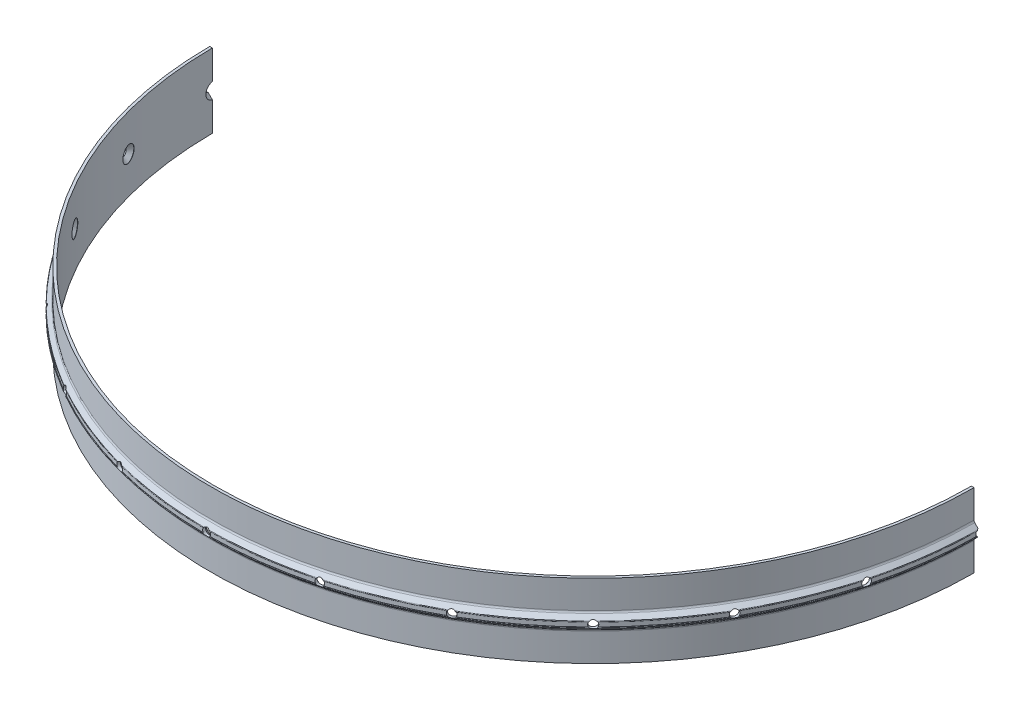
SolidWorks part; units mm, degrees
ref_plane "Front Plane" through (0, 0, 0) normal (0, 0, 1) x (1, 0, 0)
ref_plane "Top Plane" through (0, 0, 0) normal (0, 1, 0) x (1, 0, 0)
ref_plane "Right Plane" through (0, 0, 0) normal (1, 0, 0) x (0, 0, -1)
sketch "Sketch1" plane through (0, 0, 0) normal (0, 0, 1) x (1, 0, 0)
  line L0 (144.7, 34.35) -> (144.7, 23.2858)
  line L1 (-152.4, 34.35) -> (152.4, 34.35) construction
  line L2 (144.7, 23.2858) -> (146.6222, 21.3636)
  line L3 (146.6222, 21.3636) -> (146.4, 21.1414)
  line L4 (146.4, 21.1414) -> (146.4, 19.5586)
  line L5 (146.4, 19.5586) -> (146.6222, 19.3364)
  line L6 (146.6222, 19.3364) -> (144.7, 17.4142)
  line L7 (144.7, 17.4142) -> (144.7, 6.35)
  line L8 (152.4, 6.35) -> (-152.4, 6.35) construction
  line L9 (144.7, 34.35) -> (143.7, 34.35)
  line L10 (146.9107, 34.35) -> (-147.4, 34.35) construction
  line L11 (143.7, 34.35) -> (143.7, 6.35)
  line L12 (143.7, 6.35) -> (144.7, 6.35)
  line L13 (147.4, 22) -> (147.4, 34.35) construction
  line L16 (147.4, 18.7) -> (146.4, 19.7) construction
  line L17 (146.4, 21) -> (147.4, 22) construction
  line L19 (146.4, 19.7) -> (146.4, 21) construction
  line L20 (0, 0) -> (0, 37.398) construction
  line L21 (152.4, 37.398) -> (-152.4, 37.398) construction
  dimension "D1" = 1
  dimension "D2" = 2.7
  dimension "D3" = 0.1
  dimension "D4" = 0.1
  dimension "D5" = 1
  dimension "D6" = 0
revolve "Revolve1" add sketch "Sketch1" angle 180 about L20
sketch "Sketch2" plane through (0, 0, 0) normal (0, 0, 1) x (1, 0, 0)
  circle A0 centre (0, 20.35) radius 1.5
  dimension "D1" = 3
extrude "Cut-Extrude2" cut sketch "Sketch2" along normal through all
sketch "Sketch3" plane through (0, 0, 0) normal (0, 0, 1) x (1, 0, 0)
  circle A0 centre (0, 20.35) radius 3
  dimension "D1" = 6
extrude "Cut-Extrude3" cut sketch "Sketch3" along normal blind 143.764
chamfer "Chamfer1" distance 1.5 angle 45 1 edges at (1.5, 20.35, 143.764)
fillet "Fillet1" radius 0.25 4 edges at (104.0677, 21.3636, 103.2859) (104.0677, 19.3364, 103.2859) (-104.0677, 19.3364, 103.2859) (-104.0677, 21.3636, 103.2859)
fillet "Fillet2" radius 1 2 edges at (0, 17.4142, 144.7) (0, 23.2858, 144.7)
pattern_circular "CirPattern1" count 7 every 15 about axis through (0, 0, 0) along (0, 1, 0) of "Cut-Extrude3", "Cut-Extrude2", "Chamfer1"
sketch "Sketch4" plane through (0, 34.35, 0) normal (0, 1, 0) x (1, 0, 0)
  line L0 (144.7, 0) -> (143.7, 0) construction
  line L1 (164.2641, -0.5) -> (-176.002, -0.5)
  line L2 (164.2641, -0.5) -> (164.2641, 0.5)
  line L3 (164.2641, 0.5) -> (-176.002, 0.5)
  line L4 (-176.002, -0.5) -> (-176.002, 0.5)
  line L5 (164.2641, -0.5) -> (-176.002, 0.5) construction
  line L6 (164.2641, 0.5) -> (-176.002, -0.5) construction
  line L7 (-146.1358, 0) -> (-144.9929, 0) construction
  point P4 (-5.869, 0)
  dimension "D1" = 0.5
  dimension "D2" = 0.5
extrude "Cut-Extrude4" cut sketch "Sketch4" against normal through all
